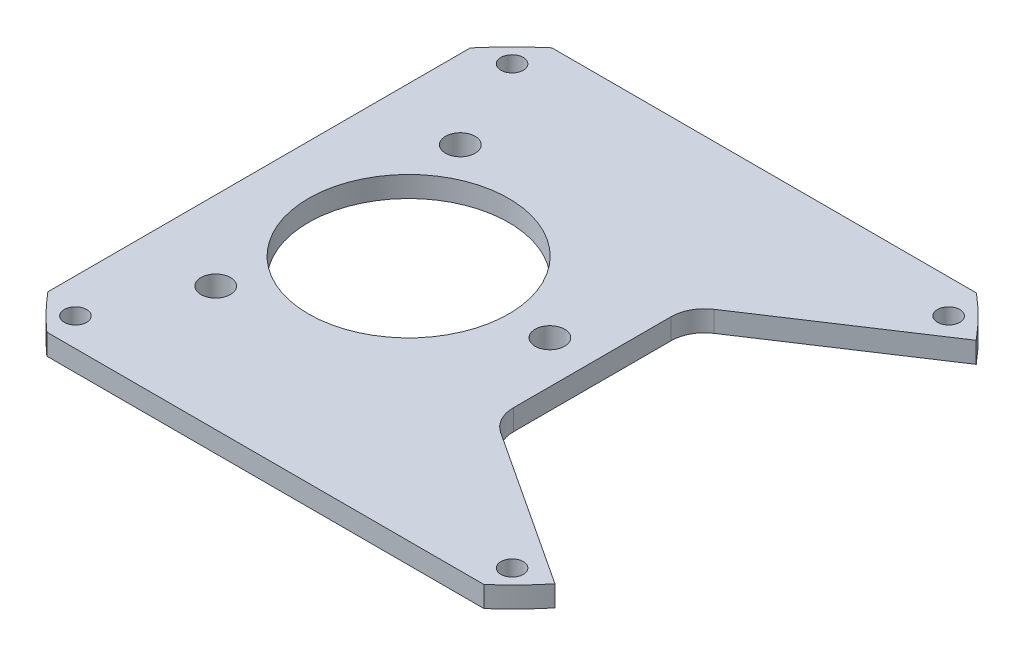
SolidWorks part; units mm, degrees
material "6061 Alloy"
ref_plane "Front Plane" through (0, 0, 0) normal (0, 0, 1) x (1, 0, 0)
ref_plane "Top Plane" through (0, 0, 0) normal (0, 1, 0) x (1, 0, 0)
ref_plane "Right Plane" through (0, 0, 0) normal (1, 0, 0) x (0, 0, -1)
sketch "Sketch1" plane through (0, 0, 0) normal (0, 1, 0) x (1, 0, 0)
  line L0 (-38.5095, 32.1488) -> (-38.5095, -32.1488)
  line L1 (-33.2269, 33.2269) -> (33.2269, 33.2269) construction
  line L2 (-33.2269, 33.2269) -> (-33.2269, -33.2269) construction
  line L3 (-33.2269, -33.2269) -> (33.2269, -33.2269) construction
  line L4 (33.2269, 33.2269) -> (33.2269, -33.2269) construction
  line L5 (-33.2269, 33.2269) -> (33.2269, -33.2269) construction
  line L6 (-33.2269, -33.2269) -> (33.2269, 33.2269) construction
  line L12 (-3.748, -12) -> (-27.748, -12) construction
  line L13 (-33.274, -37.5416) -> (33.274, -37.5416)
  line L14 (-32.3186, 38.3671) -> (32.3186, 38.3671)
  line L15 (12.2059, 14.7334) -> (12.2059, -14.7334)
  line L16 (12.2059, -14.7334) -> (38.5873, -32.0554)
  line L17 (12.2059, 14.7334) -> (38.5414, 32.1106)
  line L18 (-3.748, -12) -> (-3.748, 12) construction
  line L19 (-3.748, 12) -> (-27.748, 12) construction
  line L20 (-27.748, -12) -> (-27.748, 12) construction
  line L21 (-3.748, -12) -> (-27.748, 12) construction
  line L22 (-3.748, 12) -> (-27.748, -12) construction
  circle A0 centre (0, 0) radius 50.165 construction
  arc A2 (38.5873, -32.0554) -> (33.274, -37.5416) centre (0, 0) cw
  arc A3 (38.5414, 32.1106) -> (32.3186, 38.3671) centre (0, 0) ccw
  arc A4 (-32.3186, 38.3671) -> (-38.5095, 32.1488) centre (0, 0) ccw
  arc A5 (-33.274, -37.5416) -> (-38.5095, -32.1488) centre (0, 0) cw
  circle A6 centre (-15.748, 0) radius 21.5 construction
  circle A7 centre (-15.748, 0) radius 15.24
  point P3 (-15.748, 0)
  point P15 (12.2059, 0)
  point P24 (-15.748, 0)
  point P25 (5.752, 0)
  point P28 (-15.748, 0)
  dimension "D1" = 100.33
  dimension "D2" = 43
  dimension "D5" = 30.48
  dimension "D3" = 15.748
  dimension "D4" = 93.98
  dimension "D6" = 24
  dimension "D7" = 24
extrude "Boss-Extrude1" add sketch "Sketch1" along normal mid plane 3.175
hole_wizard "M3 Clearance Hole1" positions "Sketch2" profile "Sketch3" hole size "M3" standard "ISO" end condition through all
sketch "Sketch2" plane through (0, 1.5875, 0) normal (0, 1, 0) x (1, 0, 0)
  point P0 (-33.2269, 33.2269)
  point P3 (33.2269, 33.2269)
  point P6 (33.2269, -33.2269)
  point P9 (-33.2269, -33.2269)
sketch "Sketch3" plane through (-33.2269, 1.5875, -33.2269) normal (1, 0, 0) x (0, 0, 1)
  line L0 (0, 0) -> (0, 3.175)
  line L1 (0, 3.175) -> (1.7, 3.175)
  line L2 (1.7, 3.175) -> (1.7, 0)
  line L5 (1.7, 0) -> (0, 0)
  line L11 (0, -6.35) -> (0, 107.95) construction
  dimension "Thru Hole Dia." = 3.4
  dimension "Thru Hole Depth" = 3.175
ref_axis "Axis1" through (-15.748, 0, 0) along (0, -1, 0)
fillet "Fillet1" radius 5.08 2 edges at (12.2059, 0, -14.7334) (12.2059, 0, 14.7334)
hole_wizard "M4 Clearance Hole2" positions "Sketch4" profile "Sketch5" hole size "M4" standard "ISO" end condition through all
sketch "Sketch4" plane through (0, -1.5875, 0) normal (0, -1, 0) x (-1, 0, 0)
  point P0 (-5.752, 0)
sketch "Sketch5" plane through (5.752, -1.5875, 0) normal (1, 0, 0) x (0, 0, -1)
  line L0 (0, 0) -> (0, 3.175)
  line L1 (0, 3.175) -> (2.25, 3.175)
  line L2 (2.25, 3.175) -> (2.25, 0)
  line L5 (2.25, 0) -> (0, 0)
  line L11 (0, -6.35) -> (0, 107.95) construction
  dimension "Thru Hole Dia." = 4.5
  dimension "Thru Hole Depth" = 3.175
pattern_circular "CirPattern1" count 3 every 120 about axis through (-15.748, 0, 0) along (0, -1, 0) of "M4 Clearance Hole2"
